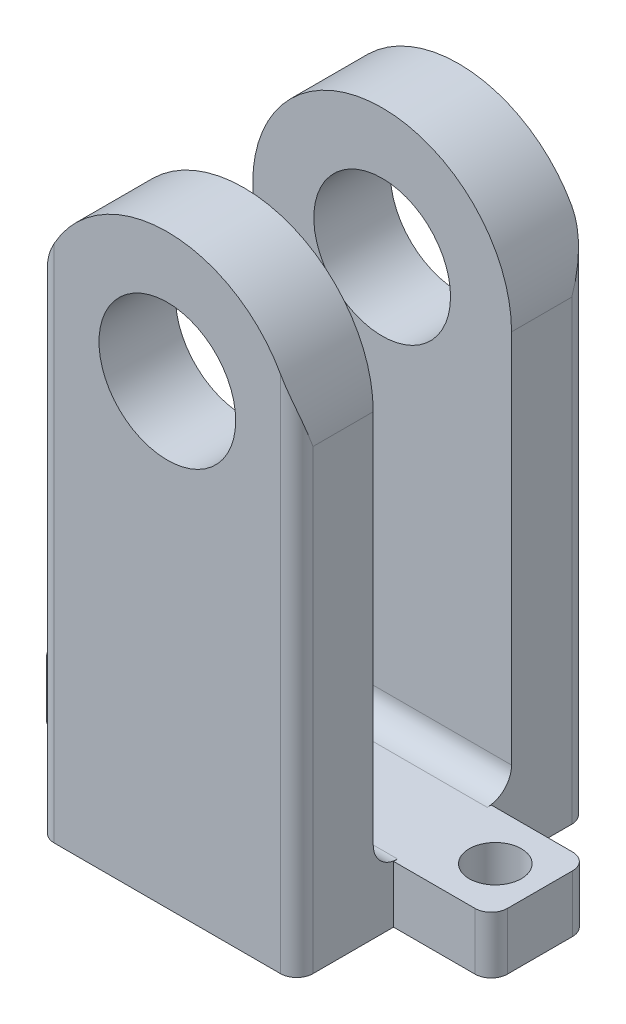
SolidWorks part; units mm, degrees
ref_plane "Alzado" through (0, 0, 0) normal (0, 0, 1) x (1, 0, 0)
ref_plane "Planta" through (0, 0, 0) normal (0, 1, 0) x (1, 0, 0)
ref_plane "Vista lateral" through (0, 0, 0) normal (1, 0, 0) x (0, 0, -1)
sketch "Holes1" plane through (0, 0, 0) normal (0, 1, 0) x (1, 0, 0)
  line L0 (0, 8.95) -> (0, -8.95) construction
  line L1 (-6.95, -8.95) -> (6.95, -8.95)
  line L2 (-7.95, -7.95) -> (-7.95, 7.95)
  line L3 (-6.95, 8.95) -> (6.95, 8.95)
  line L4 (7.95, -7.95) -> (7.95, 7.95)
  line L7 (-12.95, -3) -> (-7.95, -3)
  line L8 (-13.95, -2) -> (-13.95, 2)
  line L9 (-12.95, 3) -> (-7.95, 3)
  line L10 (-7.95, -3) -> (-7.95, 3)
  line L15 (12.95, 3) -> (7.95, 3)
  line L16 (12.95, -3) -> (7.95, -3)
  line L17 (13.95, -2) -> (13.95, 2)
  arc A1 (7.95, -7.95) -> (6.95, -8.95) centre (6.95, -7.95) cw
  arc A2 (-6.95, -8.95) -> (-7.95, -7.95) centre (-6.95, -7.95) cw
  arc A3 (7.95, 7.95) -> (6.95, 8.95) centre (6.95, 7.95) ccw
  arc A4 (-7.95, 7.95) -> (-6.95, 8.95) centre (-6.95, 7.95) cw
  arc A5 (-13.95, -2) -> (-12.95, -3) centre (-12.95, -2) ccw
  arc A6 (-13.95, 2) -> (-12.95, 3) centre (-12.95, 2) cw
  arc A7 (13.95, 2) -> (12.95, 3) centre (12.95, 2) ccw
  arc A8 (13.95, -2) -> (12.95, -3) centre (12.95, -2) cw
  circle A9 centre (11.2, 0) radius 1.6
  circle A10 centre (-11.2, 0) radius 1.6
  point P0 (0, 0)
  point P3 (0, 0)
  point P4 (13.95, 0)
  point P8 (7.95, 0)
  dimension "D5" = 22.4
  dimension "D6" = 1
  dimension "D7" = 3.2
  dimension "D1" = 6
  dimension "D2" = 6
  dimension "D3" = 15.9
  dimension "D4" = 17.9
extrude "Holes" add sketch "Holes1" along normal blind 3.5 contours A6 L8 A5 L7 L2 L9 A10 | A8 L17 A7 L15 L4 L16 A9 region at (-10.45, 0, 2.9151) region at (8.0349, 0, 0)
extrude "Boss-Extrude" add sketch "Sketch<3>" along normal blind 36 contours L0 L3 A4 L2 A2 L1 | L3 L0 L1 A1 L4 A3 region at (3.9637, 0, 0) region at (-3.9637, 0, 0)
sketch "Sketch<3>" plane through (0, 0, 0) normal (0, 1, 0) x (1, 0, 0) same geometry as "Holes1"
sketch "CUT" plane through (-7.95, 0, 0) normal (-1, 0, 0) x (0, 0, 1)
  line L0 (7.95, 36) -> (-7.95, 36) construction
  line L1 (-4.25, 36) -> (4.25, 36)
  line L2 (-4.25, 36) -> (-4.25, 5)
  line L3 (-2.75, 3.5) -> (2.75, 3.5)
  line L4 (4.25, 36) -> (4.25, 5)
  line L5 (3, 3.5) -> (-3, 3.5) construction
  arc A0 (2.75, 3.5) -> (4.25, 5) centre (2.75, 5) ccw
  arc A1 (-2.75, 3.5) -> (-4.25, 5) centre (-2.75, 5) cw
  point P8 (0, 3.5)
  point P9 (0, 3.5)
  dimension "D2" = 1.5
  dimension "D1" = 8.5
extrude "Cut-Extrude1" cut sketch "CUT" against normal through all
sketch "Hole2" plane through (0, 0, 8.95) normal (0, 0, 1) x (1, 0, 0)
  line L1 (-7.95, 36) -> (7.95, 36)
  line L2 (-7.95, 36) -> (-7.95, 0)
  line L3 (-7.95, 0) -> (7.95, 0)
  line L4 (7.95, 36) -> (7.95, 0)
  circle A0 centre (0, 28.05) radius 4.2
  arc A1 (7.95, 28.05) -> (-7.95, 28.05) centre (0, 28.05) ccw
  point P9 (0, 36)
  line M3 (6.95, 0) -> (6.95, 36)
  line M4 (6.95, 36) -> (-6.95, 36)
  line M5 (-6.95, 36) -> (-6.95, 0)
  dimension "D1" = 8.4
extrude "Cut-Extrude2" cut sketch "Hole2" against normal through all contours A0 | A1 L4 L1 M3 | A1 M3 M4 | A1 L1 L2 M5 | A1 L1 M5 region at (-7.4977, 33.2523, 8.95) region at (-5.3141, 34.8558, 8.95) region at (5.3141, 34.8558, 8.95) region at (7.4977, 33.2523, 8.95) region at (0, 28.05, 8.95)
equation "\"D1@Boss-Extrude\"=28+8"
